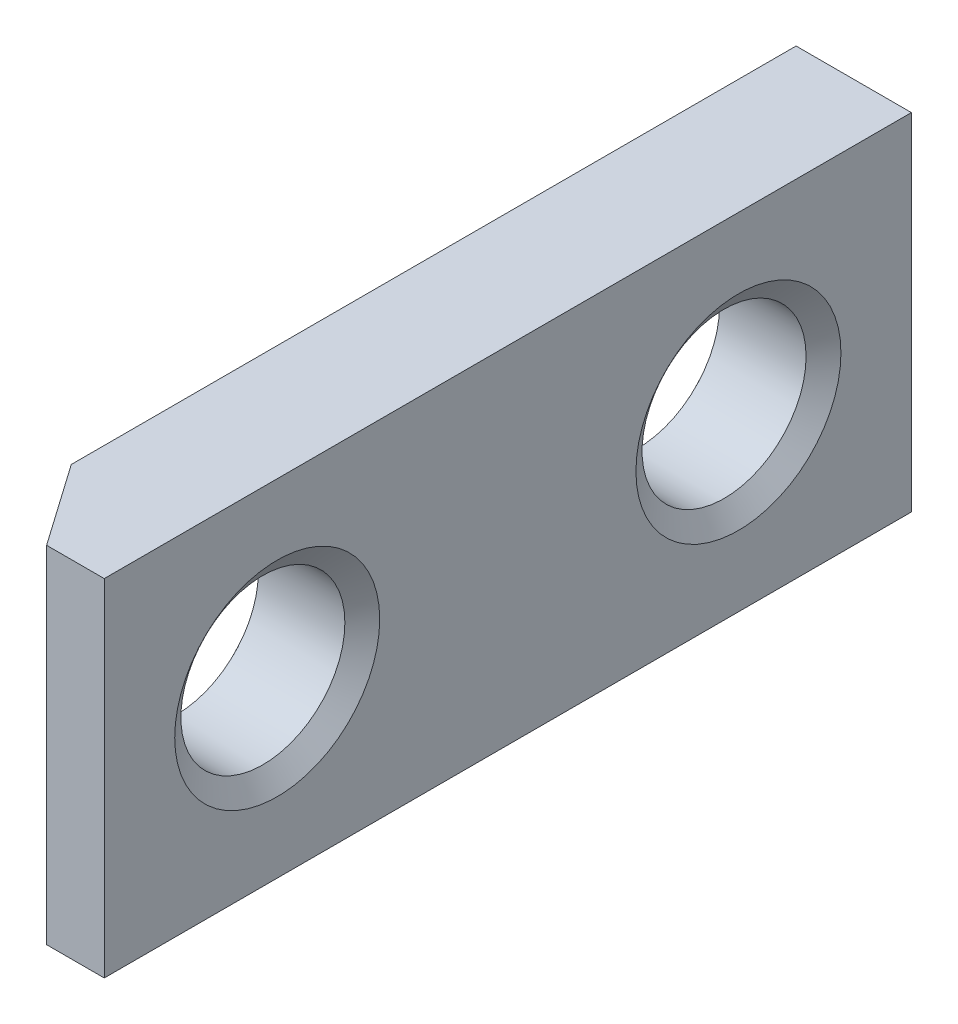
SolidWorks part; units mm, degrees
material "Простая углеродистая сталь"
ref_plane "Спереди" through (0, 0, 0) normal (0, 0, 1) x (1, 0, 0)
ref_plane "Сверху" through (0, 0, 0) normal (0, 1, 0) x (1, 0, 0)
ref_plane "Справа" through (0, 0, 0) normal (1, 0, 0) x (0, 0, -1)
sketch "Эскиз1" plane through (0, 0, 0) normal (1, 0, 0) x (0, 0, -1)
  line L1 (-7, -3) -> (7, -3)
  line L2 (-7, -3) -> (-7, 3)
  line L3 (-7, 3) -> (7, 3)
  line L4 (7, -3) -> (7, 3)
  line L5 (-7, -3) -> (7, 3) construction
  line L6 (-7, 3) -> (7, -3) construction
  point P0 (0, 0)
  dimension "D1" = 14
  dimension "D2" = 6
extrude "Бобышка-Вытянуть1" add sketch "Эскиз1" along normal blind 2
hole_wizard "Отверстие обработанное метчиком #4-401" positions "Эскиз3" profile "Эскиз4" tap size "#4-40" standard "Ansi (в дюймах)" end condition up to next
sketch "Эскиз3" plane through (2, 0, 0) normal (1, 0, 0) x (0, 0, -1)
  point P0 (-4, 0)
  point P1 (4, 0)
  dimension "D1" = 8
  dimension "D2" = 4
sketch "Эскиз4" plane through (2, 0, 4) normal (0, 1, 0) x (0, 0, -1)
  line L0 (0, 0) -> (0, 2)
  line L1 (0, 2) -> (1.778, 2)
  line L2 (1.4224, 1.751) -> (1.4224, 0.249)
  line L3 (1.4224, 0.249) -> (1.778, 0)
  line L5 (1.778, 0) -> (0, 0)
  line L6 (-1.4224, 0.249) -> (-1.778, 0) construction
  line L7 (1.778, 2) -> (1.4224, 1.751)
  line L8 (-1.778, 2) -> (-1.4224, 1.751) construction
  line L11 (0, -6.35) -> (0, 107.95) construction
  dimension "Диаметр резьбы" = 2.8448
  dimension "Глубина проходного сверла" = 2
  dimension "Диаметр передней зенковки" = 3.556
  dimension "Угол передней зенковки" = 110
  dimension "Диаметр задней зенковки" = 3.556
  dimension "Угол задней зенковки" = 110
chamfer "Фаска1" distance 1 angle 55 1 edges at (0, 0, 7) first distance on face at (1, 0, 7)
